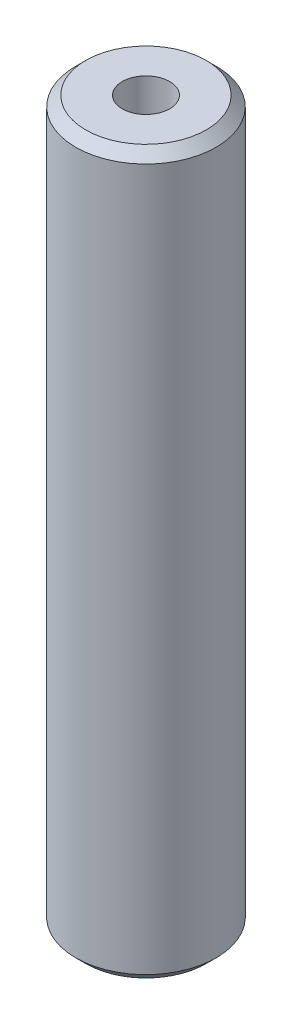
SolidWorks part; units mm, degrees
ref_plane "Front Plane" through (0, 0, 0) normal (0, 0, 1) x (1, 0, 0)
ref_plane "Top Plane" through (0, 0, 0) normal (0, 1, 0) x (1, 0, 0)
ref_plane "Right Plane" through (0, 0, 0) normal (1, 0, 0) x (0, 0, -1)
sketch "Sketch1" plane through (0, 0, 0) normal (0, 1, 0) x (1, 0, 0)
  circle A0 centre (0, 0) radius 7.5
  dimension "SHAFT_OD" = 15
extrude "Boss-Extrude1" add sketch "Sketch1" along normal blind 77.0906
sketch "Sketch2" plane through (0, 0, 0) normal (0, 1, 0) x (1, 0, 0)
  circle A0 centre (0, 0) radius 2.5295
  dimension "BORE_D" = 5.0589
extrude "Cut-Extrude1" cut sketch "Sketch2" along normal through all
chamfer "Chamfer1" distance 1.0691 angle 45 2 edges at (0, 77.0906, 7.5) (0, 0, 7.5)
